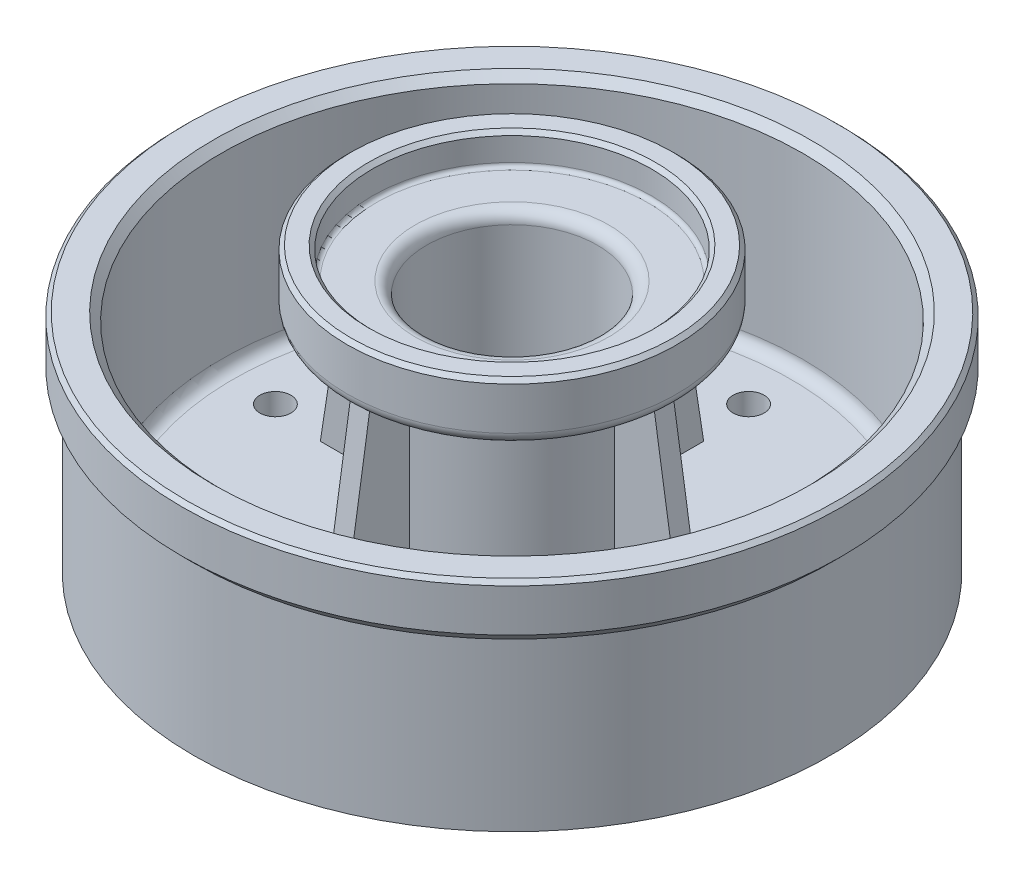
SolidWorks part; units mm, degrees
ref_plane "Front Plane" through (0, 0, 0) normal (0, 0, 1) x (1, 0, 0)
ref_plane "Top Plane" through (0, 0, 0) normal (0, 1, 0) x (1, 0, 0)
ref_plane "Right Plane" through (0, 0, 0) normal (1, 0, 0) x (0, 0, -1)
sketch "Sketch2" plane through (0, 0, 0) normal (0, 1, 0) x (1, 0, 0)
  circle A0 centre (0, 0) radius 82
  dimension "D1" = 164
extrude "Boss-Extrude1" add sketch "Sketch2" along normal blind 43
sketch "Sketch3" plane through (0, 43, 0) normal (0, 1, 0) x (1, 0, 0)
  circle A0 centre (0, 0) radius 85
extrude "Boss-Extrude2" add sketch "Sketch3" along normal blind 15
sketch "Sketch4" plane through (0, 58, 0) normal (0, 1, 0) x (1, 0, 0)
  circle A0 centre (0, 0) radius 75
  dimension "D1" = 150
extrude "Cut-Extrude1" cut sketch "Sketch4" against normal blind 51
sketch "Sketch5" plane through (0, 7, 0) normal (0, 1, 0) x (1, 0, 0)
  circle A0 centre (0, 0) radius 29
  dimension "D1" = 58
extrude "Boss-Extrude3" add sketch "Sketch5" along normal blind 51
sketch "Sketch6" plane through (0, 58, 0) normal (0, 1, 0) x (1, 0, 0)
  circle A0 centre (0, 0) radius 42.5
  dimension "D1" = 85
extrude "Boss-Extrude4" add sketch "Sketch6" along normal blind 15
sketch "Sketch7" plane through (0, 73, 0) normal (0, 1, 0) x (1, 0, 0)
  circle A0 centre (0, 0) radius 36
  circle A2 centre (0, 0) radius 22
  dimension "D1" = 72
  dimension "D2" = 44
extrude "Cut-Extrude6" cut sketch "Sketch7" against normal blind 8 contours A0
extrude "Cut-Extrude7" cut sketch "Sketch7<5>" against normal through all contours A2 region at (0, 73, 0)
sketch "Sketch7<5>" plane through (0, 73, 0) normal (0, 1, 0) x (1, 0, 0) same geometry as "Sketch7"
chamfer "Chamfer1" distance 1 angle 45 3 edges at (0, 58, 85) (0, 73, 42.5) (0, 73, 36)
chamfer "Chamfer2" distance 2 angle 45 1 edges at (0, 58, 75)
fillet "Fillet1" radius 3 6 edges at (0, 7, 29) (0, 58, 29) (0, 0, 22) (0, 65, 22) (0, 7, 75) (0, 58, 42.5)
chamfer "Chamfer3" distance 3 angle 45 1 edges at (0, 43, 85)
fillet "Fillet2" radius 1 1 edges at (0, 65, 36)
sketch "Sketch9" plane through (0, 0, 0) normal (0, 0, 1) x (1, 0, 0)
  line L0 (0, 0) -> (-48, 0)
  line L1 (-48, 0) -> (-39, 58.104)
  line L2 (-39, 58.104) -> (0, 58)
  line L3 (77, 58) -> (-77, 58) construction
  line L4 (0, 58) -> (0, 0)
  dimension "D1" = 48
  dimension "D2" = 39
sketch "Sketch10" plane through (0, 0, 0) normal (0, 1, 0) x (1, 0, 0)
  line L0 (-48, 0) -> (-48, 17.9883)
  line L1 (0, 0) -> (-48, 0) construction
ref_plane "Plane1" through (-46.8754, 7.2607, 0) normal (0.9882, -0.1531, 0) x (0, 0, -1)
sketch "Sketch11" plane through (-46.8754, 7.2607, 0) normal (0.9882, -0.1531, 0) x (0, 0, -1)
  line L0 (2.5, -1.3915) -> (-2.5, -1.3915)
  line L1 (2.5, -1.3915) -> (2.5, 56.0572)
  line L2 (2.5, 56.0572) -> (-2.5, 56.0572)
  line L3 (-2.5, 56.0572) -> (-2.5, -1.3915)
  line L5 (0, 0) -> (0, 70.2358) construction
  line L6 (0, 70.2358) -> (0, -19.1524) construction
  point P7 (2.5068, -1.3915)
  dimension "D1" = 5
  dimension "D2" = 2.5
extrude "Boss-Extrude8" add sketch "Sketch11" along normal up to surface (18.4133 mm away) up to face at (0, 10, 29)
pattern_circular "CirPattern2" count 4 over 360 about axis through (0, 58, 0) along (0, -1, 0) of "Boss-Extrude8" reverse direction yes
sketch "Sketch16" plane through (0, 7, 0) normal (0, 1, 0) x (1, 0, 0)
  line L0 (0, 0) -> (-105.2266, 0) construction
  circle A0 centre (-61, 0) radius 4
  circle A1 centre (-43.1335, 43.1335) radius 4
  circle A2 centre (0, 61) radius 4
  circle A3 centre (43.1335, 43.1335) radius 4
  circle A4 centre (61, 0) radius 4
  circle A5 centre (43.1335, -43.1335) radius 4
  circle A6 centre (0, -61) radius 4
  circle A7 centre (-43.1335, -43.1335) radius 4
  point P5 (-48.0382, 45.4387)
  point P22 (0, 0)
  dimension "D1" = 61
  dimension "D2" = 8
  dimension "D3" = 8
extrude "Cut-Extrude9" cut sketch "Sketch16" against normal through all
